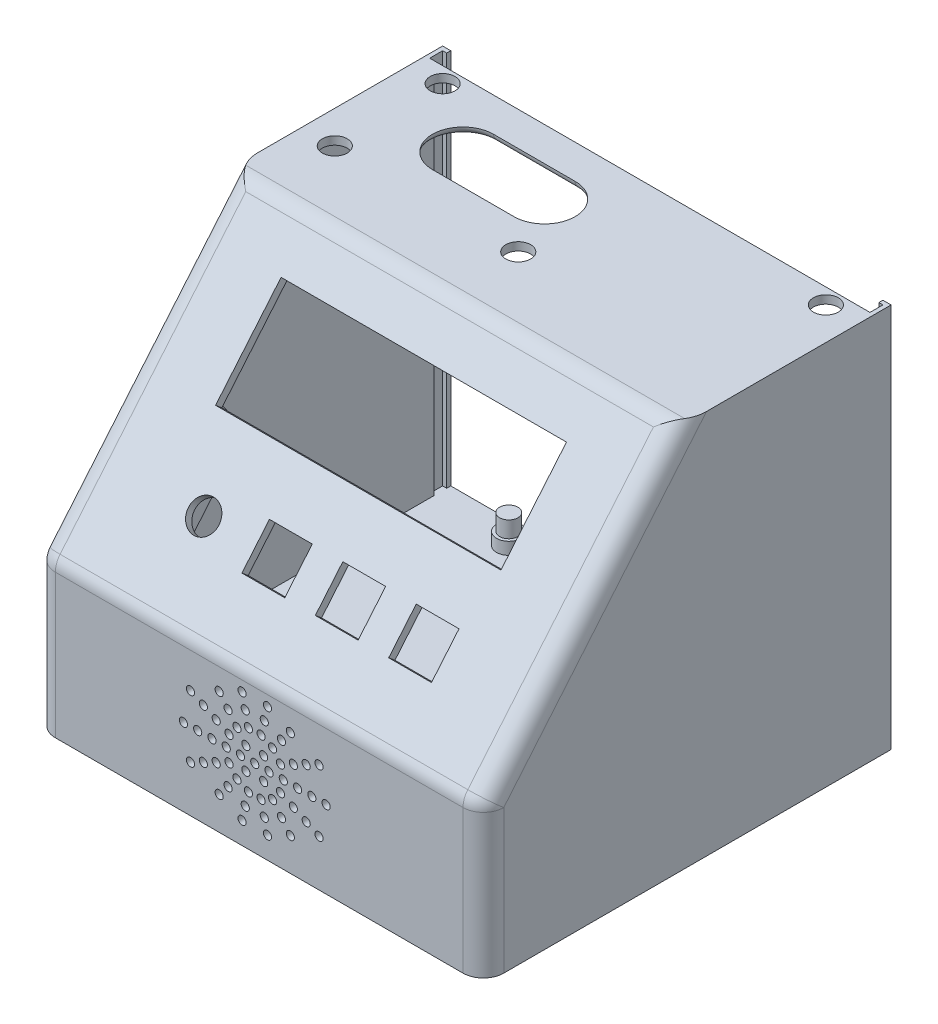
SolidWorks part; units mm, degrees
ref_plane "Front Plane" through (0, 0, 0) normal (0, 0, 1) x (1, 0, 0)
ref_plane "Top Plane" through (0, 0, 0) normal (0, 1, 0) x (1, 0, 0)
ref_plane "Right Plane" through (0, 0, 0) normal (1, 0, 0) x (0, 0, -1)
sketch "Sketch1" plane through (0, 0, 0) normal (1, 0, 0) x (0, 0, -1)
  line L0 (0, 0) -> (0, 37)
  line L1 (0, 37) -> (48.2091, 94.4533)
  line L2 (48.2091, 94.4533) -> (100, 94.4533)
  line L3 (100, 94.4533) -> (100, 0)
  line L4 (100, 0) -> (0, 0)
  dimension "D1" = 37
  dimension "D2" = 100
  dimension "D3" = 75
  dimension "D4" = 50
extrude "Boss-Extrude1" add sketch "Sketch1" along normal mid plane 110
shell "Shell1" thickness 2 removed face at (0, 47.2267, -100)
sketch "Sketch2" plane through (0, 15.2875, 18.2189) normal (0, 0.6428, 0.766) x (1, 0, 0)
  line L0 (55, 28.3436) -> (-55, 28.3436) construction
  line L1 (35, 91.161) -> (-35, 91.161)
  line L2 (35, 91.161) -> (35, 66.161)
  line L3 (35, 66.161) -> (-35, 66.161)
  line L4 (-35, 91.161) -> (-35, 66.161)
  line L5 (35, 91.161) -> (-35, 66.161) construction
  line L6 (35, 66.161) -> (-35, 91.161) construction
  line L7 (-10.39, 50.301) -> (-6.61, 50.301) construction
  line L8 (-10.39, 50.301) -> (-10.39, 46.521) construction
  line L9 (-10.39, 46.521) -> (-6.61, 46.521) construction
  line L10 (-6.61, 50.301) -> (-6.61, 46.521) construction
  line L11 (-10.39, 50.301) -> (-6.61, 46.521) construction
  line L12 (-10.39, 46.521) -> (-6.61, 50.301) construction
  line L17 (7.61, 50.301) -> (11.39, 50.301) construction
  line L18 (-14.5, 54.411) -> (-2.5, 54.411) construction
  line L23 (-14.5, 54.411) -> (-14.5, 42.411) construction
  line L24 (-14.5, 42.411) -> (-2.5, 42.411) construction
  line L26 (-2.5, 54.411) -> (-2.5, 42.411) construction
  line L27 (-14.5, 54.411) -> (-2.5, 42.411) construction
  line L28 (-14.5, 42.411) -> (-2.5, 54.411) construction
  line L29 (-13.75, 53.661) -> (-3.25, 53.661)
  line L30 (-13.75, 53.661) -> (-13.75, 43.161)
  line L31 (-13.75, 43.161) -> (-3.25, 43.161)
  line L32 (-3.25, 53.661) -> (-3.25, 43.161)
  line L33 (-13.75, 53.661) -> (-3.25, 43.161) construction
  line L34 (-13.75, 43.161) -> (-3.25, 53.661) construction
  line L35 (7.61, 50.301) -> (7.61, 46.521) construction
  line L36 (7.61, 46.521) -> (11.39, 46.521) construction
  line L37 (11.39, 50.301) -> (11.39, 46.521) construction
  line L38 (7.61, 50.301) -> (11.39, 46.521) construction
  line L39 (7.61, 46.521) -> (11.39, 50.301) construction
  line L40 (3.5, 54.411) -> (15.5, 54.411) construction
  line L41 (3.5, 54.411) -> (3.5, 42.411) construction
  line L42 (3.5, 42.411) -> (15.5, 42.411) construction
  line L43 (15.5, 54.411) -> (15.5, 42.411) construction
  line L44 (3.5, 54.411) -> (15.5, 42.411) construction
  line L45 (3.5, 42.411) -> (15.5, 54.411) construction
  line L46 (4.25, 53.661) -> (14.75, 53.661)
  line L47 (4.25, 53.661) -> (4.25, 43.161)
  line L48 (4.25, 43.161) -> (14.75, 43.161)
  line L49 (14.75, 53.661) -> (14.75, 43.161)
  line L50 (4.25, 53.661) -> (14.75, 43.161) construction
  line L51 (4.25, 43.161) -> (14.75, 53.661) construction
  line L52 (25.61, 50.301) -> (29.39, 50.301) construction
  line L53 (25.61, 50.301) -> (25.61, 46.521) construction
  line L54 (25.61, 46.521) -> (29.39, 46.521) construction
  line L55 (29.39, 50.301) -> (29.39, 46.521) construction
  line L56 (25.61, 50.301) -> (29.39, 46.521) construction
  line L57 (25.61, 46.521) -> (29.39, 50.301) construction
  line L58 (21.5, 54.411) -> (33.5, 54.411) construction
  line L59 (21.5, 54.411) -> (21.5, 42.411) construction
  line L60 (21.5, 42.411) -> (33.5, 42.411) construction
  line L61 (33.5, 54.411) -> (33.5, 42.411) construction
  line L62 (21.5, 54.411) -> (33.5, 42.411) construction
  line L63 (21.5, 42.411) -> (33.5, 54.411) construction
  line L64 (22.25, 53.661) -> (32.75, 53.661)
  line L65 (22.25, 53.661) -> (22.25, 43.161)
  line L66 (22.25, 43.161) -> (32.75, 43.161)
  line L67 (32.75, 53.661) -> (32.75, 43.161)
  line L68 (22.25, 53.661) -> (32.75, 43.161) construction
  line L69 (22.25, 43.161) -> (32.75, 53.661) construction
  line L70 (53, 102.411) -> (53, 29.0716) construction
  line L71 (-55, 103.3436) -> (-55, 28.3436) construction
  line L72 (55, 103.3436) -> (-55, 103.3436) construction
  line L73 (0, 0) -> (0, 78.661) construction
  circle A0 centre (-26.5, 48.411) radius 3.75
  circle A1 centre (-26.5, 48.411) radius 8 construction
  point P0 (0, 78.661)
  point P5 (-8.5, 48.411)
  point P10 (-8.5, 48.411)
  point P15 (-8.5, 48.411)
  point P28 (9.5, 48.411)
  point P33 (9.5, 48.411)
  point P38 (9.5, 48.411)
  point P43 (27.5, 48.411)
  point P48 (27.5, 48.411)
  point P53 (27.5, 48.411)
  dimension "D4" = 7.5
  dimension "D5" = 16
  dimension "D21" = 26.5
  dimension "D22" = 28.5
  dimension "D1" = 70
  dimension "D2" = 25
  dimension "D3" = 20.0674
  dimension "D6" = 24.6826
  dimension "D7" = 54.9326
  dimension "D8" = 3.78
  dimension "D9" = 12
  dimension "D10" = 10.5
  dimension "D11" = 3.78
  dimension "D12" = 12
  dimension "D13" = 10.5
  dimension "D14" = 3.78
  dimension "D15" = 12
  dimension "D16" = 10.5
  dimension "D17" = 18
  dimension "D18" = 18
  dimension "D19" = 18
  dimension "D20" = 25.5
extrude "Cut-Extrude1" cut sketch "Sketch2" against normal up to next
sketch "Sketch3" plane through (0, 0, 0) normal (0, 0, 1) x (1, 0, 0)
  line L0 (-20.2, 19) -> (18.04, 19) construction
  arc A0 (-6.785, 32.415) -> (-6.785, 5.585) centre (-6.785, 19) ccw construction
  arc A1 (4.625, 5.585) -> (4.625, 32.415) centre (4.625, 19) ccw construction
  circle A3 centre (-4.58, 19) radius 1
  circle A4 centre (-8.08, 19) radius 1
  circle A5 centre (-11.58, 19) radius 1
  circle A6 centre (-15.08, 19) radius 1
  circle A7 centre (-18.58, 19) radius 1
  circle A9 centre (-7.3868, 22.0372) radius 1
  circle A10 centre (-10.5402, 23.5558) radius 1
  circle A11 centre (-13.6936, 25.0744) radius 1
  circle A12 centre (-16.847, 26.593) radius 1
  circle A14 centre (-3.2622, 21.7364) radius 1
  circle A15 centre (-5.4444, 24.4728) radius 1
  circle A16 centre (-7.6266, 27.2092) radius 1
  circle A17 centre (-9.8089, 29.9456) radius 1
  circle A21 centre (-2.6376, 25.8245) radius 1
  circle A22 centre (-3.4165, 29.2367) radius 1
  circle A23 centre (-4.1953, 32.649) radius 1
  circle A27 centre (0.4776, 25.8245) radius 1
  circle A28 centre (1.2565, 29.2367) radius 1
  circle A29 centre (2.0353, 32.649) radius 1
  circle A32 centre (1.1022, 21.7364) radius 1
  circle A33 centre (3.2844, 24.4728) radius 1
  circle A34 centre (5.4666, 27.2092) radius 1
  circle A35 centre (7.6489, 29.9456) radius 1
  circle A39 centre (5.2268, 22.0372) radius 1
  circle A40 centre (8.3802, 23.5558) radius 1
  circle A41 centre (11.5336, 25.0744) radius 1
  circle A42 centre (14.687, 26.593) radius 1
  circle A44 centre (2.42, 19) radius 1
  circle A45 centre (5.92, 19) radius 1
  circle A46 centre (9.42, 19) radius 1
  circle A47 centre (12.92, 19) radius 1
  circle A48 centre (16.42, 19) radius 1
  circle A51 centre (5.2268, 15.9628) radius 1
  circle A52 centre (8.3802, 14.4442) radius 1
  circle A53 centre (11.5336, 12.9256) radius 1
  circle A54 centre (14.687, 11.407) radius 1
  circle A56 centre (1.1022, 16.2636) radius 1
  circle A57 centre (3.2844, 13.5272) radius 1
  circle A58 centre (5.4666, 10.7908) radius 1
  circle A59 centre (7.6489, 8.0544) radius 1
  circle A63 centre (0.4776, 12.1755) radius 1
  circle A64 centre (1.2565, 8.7633) radius 1
  circle A65 centre (2.0353, 5.351) radius 1
  circle A69 centre (-2.6376, 12.1755) radius 1
  circle A70 centre (-3.4165, 8.7633) radius 1
  circle A71 centre (-4.1953, 5.351) radius 1
  circle A74 centre (-3.2622, 16.2636) radius 1
  circle A75 centre (-5.4444, 13.5272) radius 1
  circle A76 centre (-7.6266, 10.7908) radius 1
  circle A77 centre (-9.8089, 8.0544) radius 1
  circle A81 centre (-7.3868, 15.9628) radius 1
  circle A82 centre (-10.5402, 14.4442) radius 1
  circle A83 centre (-13.6936, 12.9256) radius 1
  circle A84 centre (-16.847, 11.407) radius 1
  circle A85 centre (-1.08, 19) radius 1
  circle A86 centre (-11.9911, 32.6821) radius 1 [skipped]
  circle A87 centre (-4.9741, 36.0612) radius 1 [skipped]
  circle A88 centre (2.8141, 36.0612) radius 1 [skipped]
  circle A89 centre (9.8311, 32.6821) radius 1 [skipped]
  circle A90 centre (-11.9911, 5.3179) radius 1 [skipped]
  circle A91 centre (-4.9741, 1.9388) radius 1 [skipped]
  circle A92 centre (2.8141, 1.9388) radius 1 [skipped]
  circle A93 centre (9.8311, 5.3179) radius 1 [skipped]
  circle A94 centre (-4.2334, 17.4814) radius 1 [skipped]
  circle A95 centre (-4.2334, 20.5186) radius 1 [skipped]
  circle A96 centre (2.0734, 20.5186) radius 1 [skipped]
  circle A97 centre (2.0734, 17.4814) radius 1 [skipped]
  circle A98 centre (-0.3012, 15.5878) radius 1 [skipped]
  circle A99 centre (-1.8588, 15.5878) radius 1 [skipped]
  circle A100 centre (-1.8588, 22.4122) radius 1 [skipped]
  circle A101 centre (-0.3012, 22.4122) radius 1 [skipped]
  point P166 (-1.08, 19)
  dimension "D1" = 2
  dimension "D3" = 3.5
  dimension "D4" = 3.5
  dimension "D5" = 3.5
  dimension "D6" = 3.5
  dimension "D7" = 14
extrude "Cut-Extrude2" cut sketch "Sketch3" against normal up to next (2 mm away)
sketch "Sketch4" plane through (0, 94.4533, 0) normal (0, 1, 0) x (1, 0, 0)
  line L0 (-30, 80) -> (-10, 80) construction
  line L1 (-30, 87.5) -> (-10, 87.5)
  line L2 (-30, 72.5) -> (-10, 72.5)
  circle A0 centre (47, 92) radius 3.05
  circle A1 centre (-2, 65.5517) radius 3.05
  circle A2 centre (-47, 92) radius 3.05
  circle A3 centre (-47, 65.5517) radius 3.05
  arc A4 (-30, 87.5) -> (-30, 72.5) centre (-30, 80) ccw
  arc A5 (-10, 72.5) -> (-10, 87.5) centre (-10, 80) ccw
  point P16 (-20, 80)
  dimension "D1" = 6.1
extrude "Cut-Extrude3" cut sketch "Sketch4" against normal up to next
sketch "Sketch5" plane through (0, 2, 0) normal (0, 1, 0) x (1, 0, 0)
  circle A0 centre (46.5, 91.5) radius 3.05
  circle A1 centre (46.5, 8.5) radius 3.05
  circle A2 centre (-46.5, 8.5) radius 3.05
  dimension "D1" = 6.1
extrude "Cut-Extrude4" cut sketch "Sketch5" against normal up to next
sketch "Sketch6" plane through (0, 14.0019, 16.6869) normal (0, -0.6428, -0.766) x (-1, 0, 0)
  line L0 (-37.72, 55.411) -> (-37.72, 41.411) construction
  line L1 (-34.72, 55.411) -> (-34.72, 41.411)
  line L2 (-40.72, 55.411) -> (-40.72, 41.411)
  line L3 (38.28, 55.411) -> (38.28, 41.411) construction
  line L4 (41.28, 55.411) -> (41.28, 41.411)
  line L5 (35.28, 55.411) -> (35.28, 41.411)
  arc A0 (-34.72, 55.411) -> (-40.72, 55.411) centre (-37.72, 55.411) ccw
  arc A1 (-40.72, 41.411) -> (-34.72, 41.411) centre (-37.72, 41.411) ccw
  arc A2 (41.28, 55.411) -> (35.28, 55.411) centre (38.28, 55.411) ccw
  arc A3 (35.28, 41.411) -> (41.28, 41.411) centre (38.28, 41.411) ccw
  circle A4 centre (38.28, 55.411) radius 1.275
  circle A5 centre (38.28, 41.411) radius 1.275
  circle A6 centre (-37.72, 55.411) radius 1.275
  circle A7 centre (-37.72, 41.411) radius 1.275
  point P3 (-37.72, 48.411)
  point P8 (38.28, 48.411)
  dimension "D1" = 3
  dimension "D2" = 2.55
extrude "Boss-Extrude2" add sketch "Sketch6" along normal blind 10 contours L2 A1 L1 A0 A7 A6 | A6 | A7 | L5 A3 L4 A2 A5 A4 | A5 | A4 region at (37.72, 51.0869, -14.4312) region at (-38.28, 51.0869, -14.4312) region at (-38.28, 56.4492, -18.9307) region at (-38.28, 45.7246, -9.9316) region at (37.72, 56.4492, -18.9307) region at (37.72, 45.7246, -9.9316)
sketch "Sketch8" plane through (0, 2, 0) normal (0, 1, 0) x (1, 0, 0)
  circle A0 centre (32.75, 94.4776) radius 3
  circle A1 centre (32.75, 33.4776) radius 3
  circle A2 centre (-33.25, 33.4776) radius 3
  circle A3 centre (-33.25, 94.4776) radius 3
  point P12 (0, 0)
  point P13 (32.75, 94.4776)
  point P14 (0, 0)
  point P15 (-33.25, 94.4776)
  point P16 (0, 0)
  point P17 (32.75, 33.4776)
  point P18 (0, 0)
  point P19 (-33.25, 33.4776)
  dimension "D1" = 6
extrude "Boss-Extrude5" add sketch "Sketch8" along normal blind 3
sketch "Sketch9" plane through (0, 5, 0) normal (0, 1, 0) x (1, 0, 0)
  circle A0 centre (32.75, 94.4776) radius 2.25
  circle A1 centre (32.75, 33.4776) radius 2.25
  circle A2 centre (-33.25, 33.4776) radius 2.25
  circle A3 centre (-33.25, 94.4776) radius 2.25
  point P12 (0, 0)
  point P13 (32.75, 94.4776)
  point P15 (0, 0)
  point P16 (-33.25, 94.4776)
  point P17 (0, 0)
  point P18 (32.75, 33.4776)
  point P20 (0, 0)
  point P21 (-33.25, 33.4776)
  dimension "D1" = 4.5
extrude "Boss-Extrude6" add sketch "Sketch9" along normal blind 4
sketch "Sketch10" plane through (0, 14.0019, 16.6869) normal (0, -0.6428, -0.766) x (-1, 0, 0)
  circle A0 centre (-37.29, 94.851) radius 2.25
  circle A1 centre (37.71, 94.851) radius 2.25
  circle A2 centre (-37.29, 63.851) radius 2.25
  circle A3 centre (37.71, 63.851) radius 2.25
  dimension "D1" = 4.5
extrude "Boss-Extrude7" add sketch "Sketch10" along normal blind 4
fillet "Fillet1" radius 5 6 edges at (-55, 65.7267, -24.1045) (-55, 18.5, 0) (0, 37, 0) (55, 65.7267, -24.1045) (55, 18.5, 0) (0, 94.4533, -48.2091)
sketch "Sketch12" plane through (0, 94.4533, 0) normal (0, 1, 0) x (1, 0, 0)
  line L0 (55, 100) -> (55, 54.7361) construction
  line L1 (54, 95.825) -> (-54, 95.825)
  line L2 (54, 95.825) -> (54, 99)
  line L3 (54, 99) -> (52.998, 99)
  line L4 (-54, 95.825) -> (-54, 99)
  line L5 (-55, 100) -> (-55, 54.7361) construction
  line L6 (55, 100) -> (-55, 100) construction
  line L7 (52.998, 99) -> (53, 100)
  line L8 (53, 100) -> (-53, 100)
  line L9 (-53, 100) -> (-53, 99)
  line L10 (-53, 100) -> (-53, 49.1417) construction
  line L11 (-53, 99) -> (-54, 99)
  dimension "D1" = 1
  dimension "D2" = 1
  dimension "D3" = 3.175
  dimension "D4" = 1
extrude "Cut-Extrude5" cut sketch "Sketch12" against normal offset from surface (82.4533 mm away) 10 up to face at (-33.25, 2, -91.4776)
sketch "Sketch13" plane through (0, 12, 0) normal (0, 1, 0) x (1, 0, 0)
  line L4 (53, 95.825) -> (54, 95.825)
  line L5 (54, 95.825) -> (54, 99)
  line L6 (54, 99) -> (53, 99)
  line L7 (53, 99) -> (53, 95.825)
  line L8 (53, 95.825) -> (54, 95.825)
  line L9 (54, 95.825) -> (54, 99)
  line L10 (54, 99) -> (53, 99)
  line L11 (53, 99) -> (53, 95.825)
  line L12 (-53, 95.825) -> (-53, 99)
  line L13 (-53, 99) -> (-54, 99)
  line L14 (-54, 99) -> (-54, 95.825)
  line L15 (-54, 95.825) -> (-53, 95.825)
  line L16 (-53, 95.825) -> (-53, 99)
  line L17 (-53, 99) -> (-54, 99)
  line L18 (-54, 99) -> (-54, 95.825)
  line L19 (-54, 95.825) -> (-53, 95.825)
  dimension "D1" = 0
  dimension "D2" = 0
extrude "Cut-Extrude6" cut sketch "Sketch13" against normal up to surface (10 mm away) up to face at (-33.25, 2, -91.4776)
fillet "Fillet3" radius 2 4 edges at (-37.5, 92.4533, -80) (-20, 92.4533, -87.5) (-2.5, 92.4533, -80) (-20, 92.4533, -72.5)
